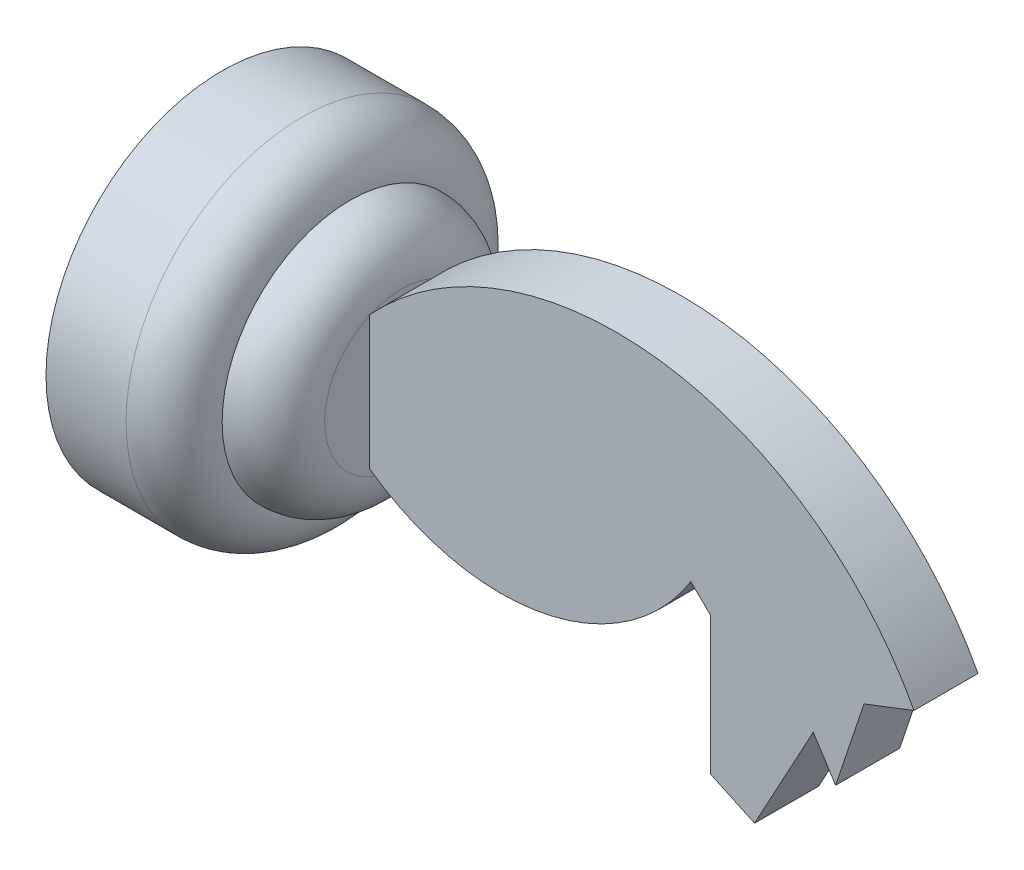
SolidWorks part; units mm, degrees
ref_plane "Спереди" through (0, 0, 0) normal (0, 0, 1) x (1, 0, 0)
ref_plane "Сверху" through (0, 0, 0) normal (0, 1, 0) x (1, 0, 0)
ref_plane "Справа" through (0, 0, 0) normal (1, 0, 0) x (0, 0, -1)
other "Configuration Table"
sketch "Эскиз1" plane through (0, 0, 0) normal (0, 0, 1) x (1, 0, 0)
  line L0 (0, 0) -> (71.2267, 0) construction
sketch "попа" plane through (0, 0, 0) normal (0, 0, 1) x (1, 0, 0)
  line L0 (0, 0) -> (0, 11)
  line L1 (0, 11) -> (5, 11)
  line L3 (0, 0) -> (71.2267, 0) construction
  line L4 (5, 0) -> (0, 0)
  line L7 (11.2, 4.8) -> (11.2, 0)
  line L8 (11.2, 0) -> (0, 0)
  line L9 (8, 0) -> (8, 8)
  line L10 (11.2, 2.4) -> (11.2, 0)
  line L11 (11.2, 4.3) -> (11.2, 0)
  line L12 (11.2, 0) -> (45.2, 0)
  arc A0 (8, 8) -> (5, 11) centre (5, 8) ccw
  arc A1 (11.2, 4.8) -> (8, 8) centre (8, 4.8) ccw
  point P13 (0, 0)
  dimension "D6" = 3
  dimension "D7" = 3.2
  dimension "D1" = 8
  dimension "D2" = 5
  dimension "D3" = 11.2
  dimension "D4" = 4.8
  dimension "D5" = 8
revolve "Повернуть1" add sketch "попа" angle 360 about L0 region at (3.9253, 5.3916, 0) region at (9.5169, 3.6915, 0)
sketch "вверх" plane through (0, 0, 0) normal (0, 0, 1) x (1, 0, 0)
  line L0 (11.2, 0) -> (11.2, 4.4)
  line L1 (11.2, -4.8) -> (11.2, 4.8) construction
  line L2 (11.2, 0) -> (45.2, 0)
  line L3 (0, 0) -> (71.2267, 0) construction
  line L5 (11.2, 0) -> (11.2, -3.915)
  line L6 (42.083, -1.2) -> (42.083, 0)
  line L7 (40.3075, -6.49) -> (40.3075, 0)
  line L8 (38.912, -4.32) -> (38.912, 0)
  line L9 (31.2635, 0) -> (32.499, -1.1973)
  line L10 (32.499, -1.1973) -> (32.499, -9.7973)
  line L11 (32.499, -9.7973) -> (35.2487, -11.07)
  line L12 (35.2487, -11.07) -> (38.912, -4.32)
  line L13 (38.912, -4.32) -> (40.3075, -6.49)
  line L14 (40.3075, -6.49) -> (42.083, -1.2)
  line L15 (42.083, -1.2) -> (45.2, 0)
  line L16 (35.2487, -11.07) -> (35.2487, 0)
  arc A1 (31.2635, 0) -> (11.2, -3.915) centre (19.3994, 7.4327) cw
  arc A2 (11.2, 4.4) -> (45.2, 0) centre (26.6431, -9.8306) cw
  dimension "D3" = 21
  dimension "D6" = 14
  dimension "D7" = 8.6
  dimension "D1" = 4.4
  dimension "D2" = 34
  dimension "D4" = 20.0635
  dimension "D5" = 3.915
  dimension "D8" = 1.7204
  dimension "D9" = 3.03
  dimension "D10" = 7.68
  dimension "D11" = 2.58
  dimension "D12" = 5.58
  dimension "D13" = 3.34
  dimension "D14" = 13.9365
  dimension "D15" = 1.2
  dimension "D16" = 6.49
  dimension "D17" = 4.32
  dimension "D18" = 11.07
extrude "Бобышка-Вытянуть2" add sketch "вверх" along normal mid plane 4 contours A2 L0 L2 | A1 L2 L5 | L16 L12 L8 L2 | L11 L16 L2 L9 L10 | L7 L14 L6 L2 | L8 L13 L7 L2 | L6 L15 L2 region at (27.0721, 4.6677, 0) region at (20.1547, -2.7915, 0) region at (33.8562, -5.102, 0) region at (43.122, -0.4, 0) region at (36.8126, -4.0942, 0) region at (40.9917, -2.2258, 0) region at (39.6565, -2.7388, 0)
